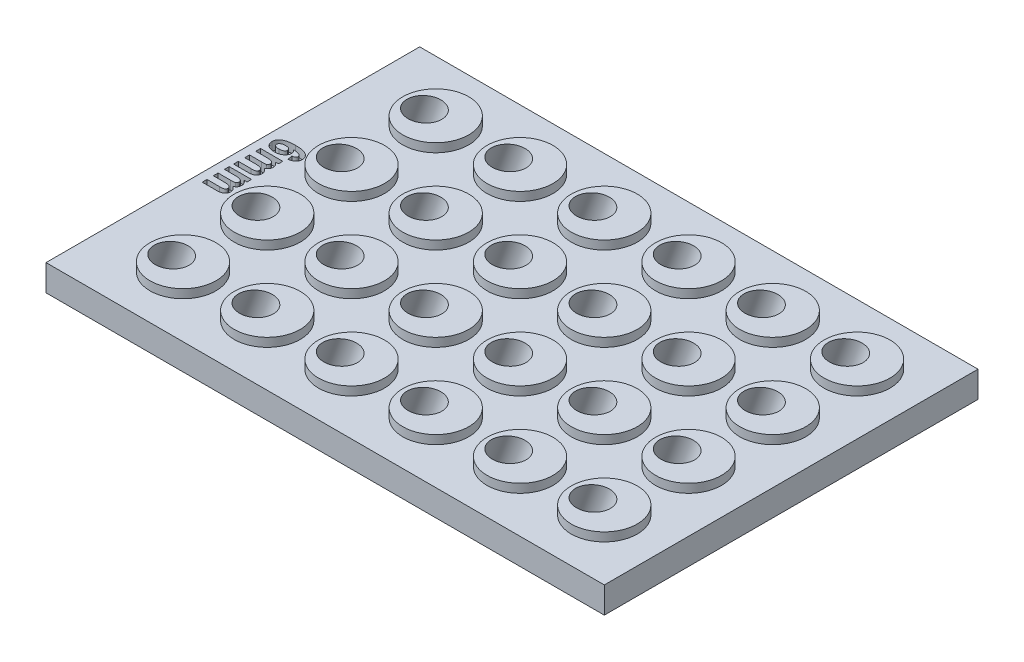
SolidWorks part; units mm, degrees
material "PVC Rigid"
ref_plane "Front Plane" through (0, 0, 0) normal (0, 0, 1) x (1, 0, 0)
ref_plane "Top Plane" through (0, 0, 0) normal (0, 1, 0) x (1, 0, 0)
ref_plane "Right Plane" through (0, 0, 0) normal (1, 0, 0) x (0, 0, -1)
ref_plane "Top of 24 well plate" through (0, 6, 0) normal (0, 1, 0) x (1, 0, 0)
ref_plane "Bottom of 24 well plate" through (0, 23.5, 0) normal (0, 1, 0) x (1, 0, 0)
ref_plane "Middle of 24 well plate" through (0, 14.75, 0) normal (0, 1, 0) x (1, 0, 0)
sketch "Sketch1" plane through (0, 0, 0) normal (0, 1, 0) x (1, 0, 0)
  line L1 (-63.945, 42.8) -> (63.945, 42.8)
  line L2 (-63.945, 42.8) -> (-63.945, -42.8)
  line L3 (-63.945, -42.8) -> (63.945, -42.8)
  line L4 (63.945, 42.8) -> (63.945, -42.8)
  line L5 (-63.945, 42.8) -> (63.945, -42.8) construction
  line L6 (-63.945, -42.8) -> (63.945, 42.8) construction
  point P0 (0, 0)
  dimension "D1" = 127.89
  dimension "D2" = 85.6
extrude "Main Plate" add sketch "Sketch1" along normal up to surface (6 mm away) up to plane "Top of 24 well plate"
sketch "Wells_LSP" plane through (0, 6, 0) normal (0, 1, 0) x (1, 0, 0)
  line L0 (-46.425, 28.96) -> (-27.125, 28.96) construction
  line L4 (63.945, 42.8) -> (-63.945, 42.8) construction
  line L5 (-63.945, 42.8) -> (-63.945, -42.8) construction
  circle A0 centre (-46.425, 28.96) radius 7.56
  circle A1 centre (-27.125, 28.96) radius 7.56
  circle A2 centre (-7.825, 28.96) radius 7.56
  circle A3 centre (11.475, 28.96) radius 7.56
  circle A4 centre (30.775, 28.96) radius 7.56
  circle A5 centre (50.075, 28.96) radius 7.56
  circle A6 centre (-27.125, 9.66) radius 7.56
  circle A7 centre (-7.825, 9.66) radius 7.56
  circle A8 centre (11.475, 9.66) radius 7.56
  circle A9 centre (30.775, 9.66) radius 7.56
  circle A10 centre (50.075, 9.66) radius 7.56
  circle A11 centre (-27.125, -9.64) radius 7.56
  circle A12 centre (-7.825, -9.64) radius 7.56
  circle A13 centre (11.475, -9.64) radius 7.56
  circle A14 centre (30.775, -9.64) radius 7.56
  circle A15 centre (50.075, -9.64) radius 7.56
  circle A16 centre (-27.125, -28.94) radius 7.56
  circle A17 centre (-7.825, -28.94) radius 7.56
  circle A18 centre (11.475, -28.94) radius 7.56
  circle A19 centre (30.775, -28.94) radius 7.56
  circle A20 centre (50.075, -28.94) radius 7.56
  circle A21 centre (-46.425, 9.66) radius 7.56
  circle A22 centre (-46.425, -9.64) radius 7.56
  circle A23 centre (-46.425, -28.94) radius 7.56
  dimension "D2" = 6
  dimension "D4" = 4
  dimension "D7" = 15.12
  dimension "D16" = 17.52
  dimension "D3" = 19.3
  dimension "D15" = 13.84
extrude "Boss-Extrude1" add sketch "Wells_LSP" along normal blind 2
ref_point "Point1"
ref_plane "Plane1" through (0, 0, -28.96) normal (0, 0, -1) x (-1, 0, 0)
sketch "Sketch2" plane through (0, 0, -28.96) normal (0, 0, -1) x (-1, 0, 0)
  line L0 (46.425, 8) -> (46.425, 0) construction
  line L1 (43.8417, 22.2174) -> (47.3655, 23.5)
  line L2 (43.8417, 22.2174) -> (52.395, -1.2826)
  line L3 (52.395, -1.2826) -> (55.9188, 0)
  line L4 (47.3655, 23.5) -> (55.9188, 0)
  line L5 (53.985, 8) -> (38.865, 8) construction
  line L6 (-63.945, 0) -> (63.945, 0) construction
  line L7 (47.08, 23.5) -> (-47.08, 23.5) construction
  line L8 (55, 14.75) -> (-55, 14.75) construction
  line L9 (47.08, 6) -> (-47.08, 6) construction
  point P10 (53.735, 6)
  point P13 (46.425, 14.75)
  dimension "D1" = 20
  dimension "D2" = 3.75
  dimension "D3" = 7.31
revolve "Cut-Revolve1" cut sketch "Sketch2" angle 360 about L2
pattern_linear "LPattern1" count 4 spacing 19.3 along (0, 0, 1) count 6 spacing 19.3 along (1, 0, 0) of "Cut-Revolve1"
sketch "Sketch3" plane through (0, 6, 0) normal (0, 1, 0) x (1, 0, 0)
  line L0 (-62.0038, 42.8) -> (-62.0038, -42.8) construction
  line L1 (63.945, 42.8) -> (-63.945, 42.8) construction
  line L2 (-63.945, -42.8) -> (63.945, -42.8) construction
  text T0 "6mm" font "Arial Narrow" height 7
extrude "Cut-Extrude1" cut sketch "Sketch3" against normal blind 2 from surface starting at face at (-46.425, 6, 36.5)
equation "\"D1\"= 0.32"
equation "\"D1\"= 1.27 - 0.32"
equation "\"D3@Sketch2\"=15.62/2-.5"
